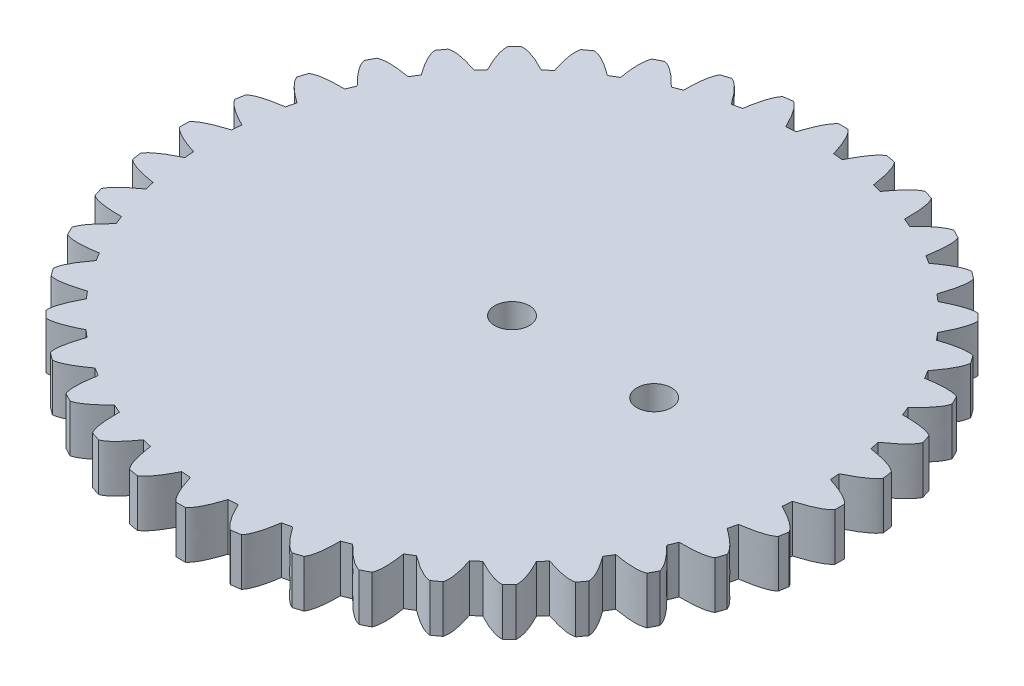
SolidWorks part; units mm, degrees
material "ABS"
ref_plane "Front Plane" through (0, 0, 0) normal (0, 0, 1) x (1, 0, 0)
ref_plane "Top Plane" through (0, 0, 0) normal (0, 1, 0) x (1, 0, 0)
ref_plane "Right Plane" through (0, 0, 0) normal (1, 0, 0) x (0, 0, -1)
sketch "Sketch1" plane through (0, 0, 0) normal (0, 1, 0) x (1, 0, 0)
  line L0 (21.1871, 23.7554) -> (23.9973, 20.9127) construction
  line L2 (22.5922, 22.334) -> (24.7257, 24.4431) construction
  line L3 (24.7257, 24.4431) -> (24.8654, 24.5812)
  circle A0 centre (0, 0) radius 31.831
  circle A1 centre (0, 0) radius 34.7682
  spline S0 degree 2 poles (23.9973, 20.9127) (27.1386, 26.8284) (21.1871, 23.7554) knots 0 0 0 1 1 1
  point P3 (21.1871, 23.7554)
  point P4 (23.9973, 20.9127)
  point P6 (24.3716, 24.7962)
  point P12 (20.4304, 24.4092)
  point P14 (24.8654, 24.5812)
  point P15 (25.0746, 24.085)
  point P16 (13.455, 28.8474)
  dimension "D1" = 63.662
  dimension "D4" = 3
  dimension "D5" = 1
  dimension "D2" = 4
  dimension "D3" = 1
extrude "Boss-Extrude4" add sketch "Sketch1" along normal blind 5 contours A0 | A0 S0 A1 region at (23.4992, 0, -23.2307) region at (0, 0, 0)
pattern_circular "CirPattern6" count 40 every 9 about axis through (0, 5, 0) along (0, 1, 0) of "Boss-Extrude4"
sketch "Sketch2" plane through (0, 5, 0) normal (0, 1, 0) x (1, 0, 0)
  circle A0 centre (0, 0) radius 1.825
  circle A1 centre (15, 0) radius 1.825
  dimension "D1" = 3.65
  dimension "D2" = 3.65
  dimension "D3" = 15
extrude "Cut-Extrude1" cut sketch "Sketch2" against normal up to surface (5 mm away) up to face at (0, 0, 0)
equation "\"number-of-teeth\"= 40"
equation "\"gear-size\"= 4mm"
equation "\"circumference\"= \"number-of-teeth\" * ( ( 1 + \"space-between-teeth\" ) * \"gear-size\" )"
equation "\"space-between-teeth\"= .25"
equation "\"D1@Sketch1\" = \"circumference\" / pi"
equation "\"D2@Sketch1\"=\"gear-size\""
equation "\"gear-length\"= 3mm"
equation "\"D4@Sketch1\"=\"gear-length\""
equation "\"D5@Sketch1\"=\"gear-size\" * \"space-between-teeth\""
equation "\"D3@Sketch1\"=\"gear-size\" * \"space-between-teeth\""
equation "\"D1@CirPattern6\"=\"number-of-teeth\""
equation "\"D2@CirPattern6\"=360 / \"number-of-teeth\""
